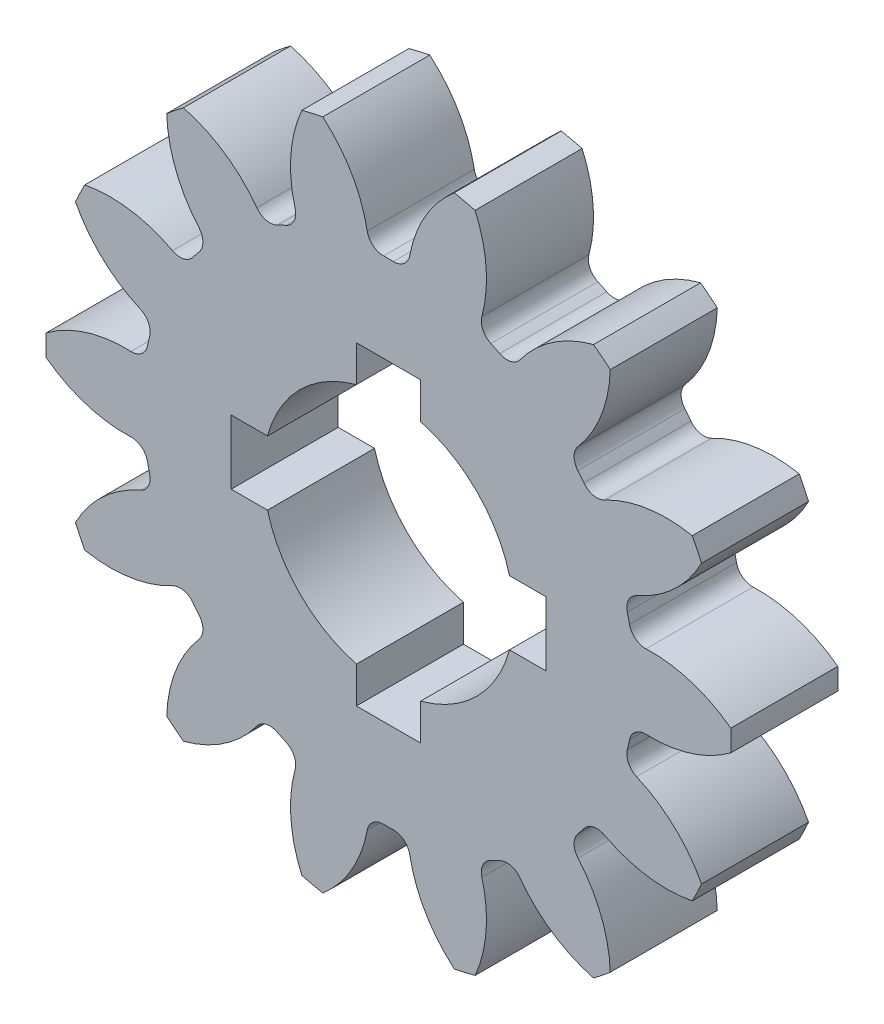
SolidWorks part; units mm, degrees
ref_plane "Front Plane" through (0, 0, 0) normal (0, 0, 1) x (1, 0, 0)
ref_plane "Top Plane" through (0, 0, 0) normal (0, 1, 0) x (1, 0, 0)
ref_plane "Right Plane" through (0, 0, 0) normal (1, 0, 0) x (0, 0, -1)
sketch "Sketch1" plane through (0, 0, 0) normal (0, 0, 1) x (1, 0, 0)
  line L4 (-0.9046, 11.4644) -> (0, 0) construction
  line L5 (0, 0) -> (0, 16) construction
  line L6 (0, 0) -> (3.5603, 15.5988) construction
  line L7 (-1.6208, 13.9059) -> (0.711, 15.076) construction
  line L8 (-1.6208, 13.9059) -> (0.3908, 14.1403) construction
  line L11 (1.6208, 13.9059) -> (-1.6208, 13.9059) construction
  circle A0 centre (0, 0) radius 11.5
  circle A1 centre (0, 0) radius 14 construction
  circle A2 centre (0, 0) radius 16
  arc A3 (-3.0712, 15.7025) -> (-0.9046, 11.4644) centre (-7.0873, 10.9765) cw
  arc A4 (3.0712, 15.7025) -> (0.9046, 11.4644) centre (7.0873, 10.9765) ccw
  point P5 (-14, 0)
  point P6 (-16, 0)
  point P7 (-11.5, 0)
  point P12 (-1.6208, 13.9059)
  point P22 (1.6208, 13.9059)
  dimension "D5" = 28
  dimension "D1" = 2.5
  dimension "D2" = 2
  dimension "D3" = 20
  dimension "D4" = 3.2416
  dimension "D6" = 12.857
  dimension "D7" = 0.5
extrude "Boss-Extrude1" add sketch "Sketch1" against normal blind 5 contours A2
extrude "Cut-Extrude1" cut sketch "Sketch1<4>" against normal blind 10 contours A4 A2 A3 A0 region at (0, 14.1868, 0)
sketch "Sketch1<4>" plane through (0, 0, 0) normal (0, 0, 1) x (1, 0, 0) same geometry as "Sketch1"
fillet "Fillet2" radius 0.76 2 edges at (0.9046, 11.4644, -2.5) (-0.9046, 11.4644, -2.5)
ref_axis "Axis1" through (0, 0, 0) along (0, 0, 1)
pattern_circular "CirPattern2" count 14 over 360 about axis through (0, 0, 0) along (0, 0, 1) of "Cut-Extrude1", "Fillet2"
sketch "Sketch2" plane through (0, 0, 0) normal (0, 0, 1) x (1, 0, 0)
  line L0 (-1.5, 5.6528) -> (-1.5, 7.3485)
  line L1 (-1.5, 4.3485) -> (1.5, 4.3485) construction
  line L2 (-1.5, 4.3485) -> (-1.5, 7.3485) construction
  line L3 (-1.5, 7.3485) -> (1.5, 7.3485) construction
  line L4 (1.5, 4.3485) -> (1.5, 7.3485) construction
  line L5 (-1.5, 4.3485) -> (1.5, 7.3485) construction
  line L6 (-1.5, 7.3485) -> (1.5, 4.3485) construction
  line L7 (4.3485, -1.5) -> (7.3485, -1.5) construction
  line L8 (4.3485, -1.5) -> (4.3485, 1.5) construction
  line L9 (4.3485, 1.5) -> (7.3485, 1.5) construction
  line L10 (7.3485, -1.5) -> (7.3485, 1.5) construction
  line L11 (4.3485, -1.5) -> (7.3485, 1.5) construction
  line L12 (4.3485, 1.5) -> (7.3485, -1.5) construction
  line L13 (-1.5, -7.3485) -> (1.5, -7.3485) construction
  line L14 (-1.5, -7.3485) -> (-1.5, -4.3485) construction
  line L15 (-1.5, -4.3485) -> (1.5, -4.3485) construction
  line L16 (1.5, -7.3485) -> (1.5, -4.3485) construction
  line L17 (-1.5, -7.3485) -> (1.5, -4.3485) construction
  line L18 (-1.5, -4.3485) -> (1.5, -7.3485) construction
  line L19 (-7.3485, -1.5) -> (-4.3485, -1.5) construction
  line L20 (-7.3485, -1.5) -> (-7.3485, 1.5) construction
  line L21 (-7.3485, 1.5) -> (-4.3485, 1.5) construction
  line L22 (-4.3485, -1.5) -> (-4.3485, 1.5) construction
  line L23 (-7.3485, -1.5) -> (-4.3485, 1.5) construction
  line L24 (-7.3485, 1.5) -> (-4.3485, -1.5) construction
  line L25 (-1.5, 7.3485) -> (1.5, 7.3485)
  line L26 (1.5, 7.3485) -> (1.5, 5.6528)
  line L27 (5.6528, 1.5) -> (7.3485, 1.5)
  line L28 (7.3485, 1.5) -> (7.3485, -1.5)
  line L29 (7.3485, -1.5) -> (5.6528, -1.5)
  line L30 (1.5, -7.3485) -> (1.5, -5.6528)
  line L31 (1.5, -7.3485) -> (-1.5, -7.3485)
  line L32 (-1.5, -7.3485) -> (-1.5, -5.6528)
  line L33 (-5.6528, -1.5) -> (-7.3485, -1.5)
  line L34 (-7.3485, -1.5) -> (-7.3485, 1.5)
  line L35 (-7.3485, 1.5) -> (-5.6528, 1.5)
  circle A0 centre (0, 0) radius 7.5 construction
  arc A1 (-1.5, 5.6528) -> (-5.6528, 1.5) centre (0, 0) ccw
  arc A2 (5.6528, 1.5) -> (1.5, 5.6528) centre (0, 0) ccw
  arc A3 (1.5, -5.6528) -> (5.6528, -1.5) centre (0, 0) ccw
  arc A4 (-5.6528, -1.5) -> (-1.5, -5.6528) centre (0, 0) ccw
  point P3 (0, 5.8485)
  point P8 (5.8485, 0)
  point P13 (0, -5.8485)
  point P18 (-5.8485, 0)
  dimension "D1" = 15
  dimension "D2" = 3
extrude "Cut-Extrude2" cut sketch "Sketch2" against normal up to surface (5 mm away) up to face at (0, 0, -5)
equation "\"backlash\"= 0.1mm"
equation "\"module\"= 2mm"
equation "\"pressureAngle\"= 20deg"
equation "\"width\"= 10mm"
equation "\"D1@Sketch1\"= 1.25 * \"module\""
equation "\"D2@Sketch1\"=\"module\""
equation "\"D5@Sketch1\"=\"module\"*\"numberOfTeeth\""
equation "\"D1@Boss-Extrude1\"=\"width\"-5"
equation "\"D3@Sketch1\"=\"pressureAngle\""
equation "\"D1@Cut-Extrude1\"=\"width\""
equation "\"D1@CirPattern2\"=\"numberOfTeeth\""
equation "\"D1@Fillet2\"=0.38*\"module\""
equation "\"D4@Sketch1\"=pi*\"module\"/2+\"backlash\""
equation "\"numberOfTeeth\"= 14"
equation "\"D6@Sketch1\"=180/\"numberOfTeeth\""
equation "\"toothTipProfile\"= 1mm"
equation "\"D7@Sketch1\"=\"toothTipProfile\"/2"
equation "\"lengthOverallRack\"= pi * \"module\" * \"numberOfTeethRack\""
equation "\"numberOfTeethRack\"= 20"
